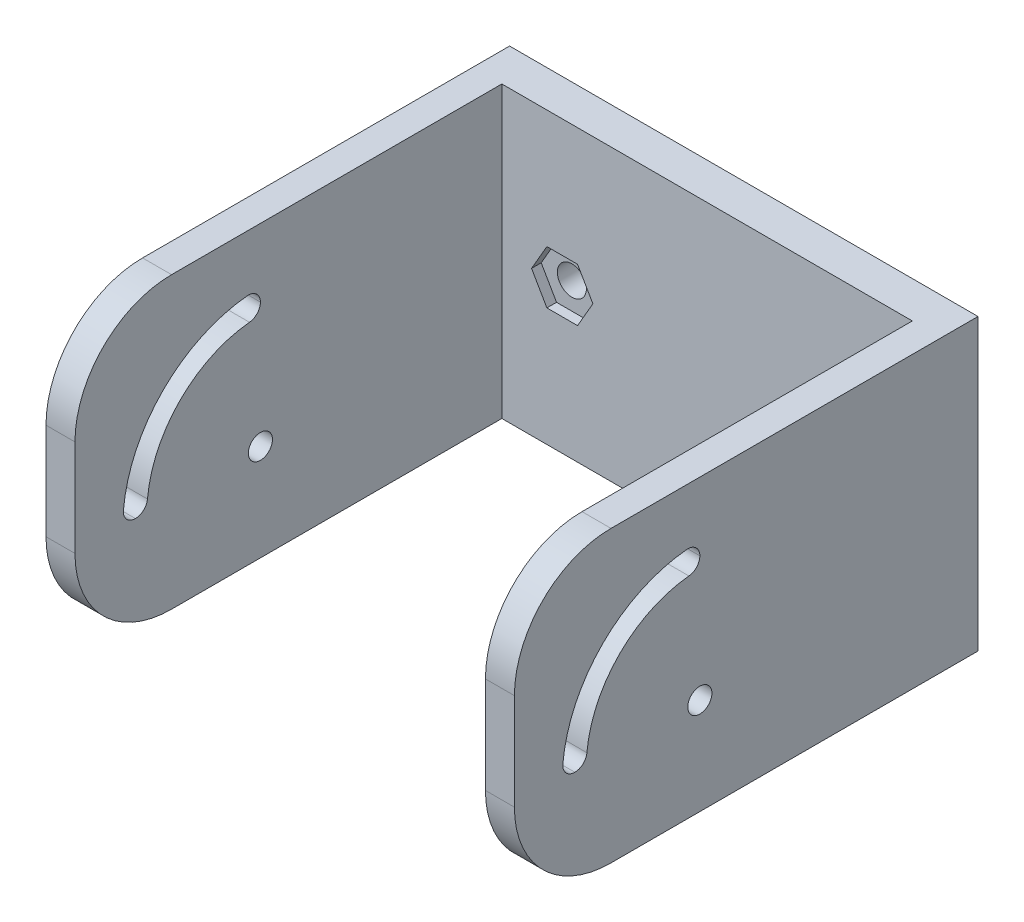
SolidWorks part; units mm, degrees
ref_plane "Front Plane" through (0, 0, 0) normal (0, 0, 1) x (1, 0, 0)
ref_plane "Top Plane" through (0, 0, 0) normal (0, 1, 0) x (1, 0, 0)
ref_plane "Right Plane" through (0, 0, 0) normal (1, 0, 0) x (0, 0, -1)
sketch "Sketch2" plane through (0, 0, 0) normal (0, 1, 0) x (1, 0, 0)
  line L0 (26.1154, 19.3846) -> (-22.3846, 19.3846)
  line L1 (-22.3846, 19.3846) -> (-22.3846, -28.6154)
  line L2 (-22.3846, -28.6154) -> (-19.3846, -28.6154)
  line L3 (-19.3846, -28.6154) -> (-19.3846, 15.5846)
  line L4 (-19.3846, 15.5846) -> (23.1154, 15.5846)
  line L5 (23.1154, 15.5846) -> (23.1154, -28.6154)
  line L6 (23.1154, -28.6154) -> (26.1154, -28.6154)
  line L7 (26.1154, -28.6154) -> (26.1154, 19.3846)
  dimension "D1" = 3
  dimension "D2" = 3
  dimension "D3" = 3.8
  dimension "D4" = 42.5
  dimension "D5" = 48
extrude "Boss-Extrude1" add sketch "Sketch2" along normal blind 30
sketch "Sketch3" plane through (-19.3846, 0, 0) normal (1, 0, 0) x (0, 0, -1)
  line L1 (15.5846, 30) -> (15.5846, 0) construction
  line L2 (-9.4154, 10) -> (-9.4154, 11.25)
  line L3 (-9.4154, 10) -> (-10.6654, 10)
  line L4 (-9.4154, 21.75) -> (-9.4154, 29.1907)
  line L5 (-21.1654, 10) -> (-23.6654, 10)
  line L6 (-28.6154, 0) -> (15.5846, 0) construction
  circle A0 centre (-9.4154, 10) radius 1.25
  arc A1 (-9.4154, 24.25) -> (-23.6654, 10) centre (-9.4154, 10) ccw
  arc A2 (-9.4154, 21.75) -> (-21.1654, 10) centre (-9.4154, 10) ccw
  point P11 (0, 0)
  dimension "D1" = 2.5
  dimension "D2" = 2.5
  dimension "D4" = 10.5
  dimension "D3" = 25
  dimension "D5" = 90
  dimension "D6" = 10
extrude "Cut-Extrude1" cut sketch "Sketch3" against normal blind 10 and the other way through all contours A2 L4 A1 L5 | L3 A0 L2 | L2 A0 L3 region at (-19.3846, 10.5305, 9.9459) region at (-19.3846, 9.8232, 9.2385) region at (-19.3846, 18.451, 17.8664)
sketch "Sketch4" plane through (0, 0, -19.3846) normal (0, 0, -1) x (-1, 0, 0)
  line L0 (-26.1154, 15) -> (22.3846, 15) construction
  line L1 (22.3846, 30) -> (22.3846, 0) construction
  line L2 (-1.8654, 30) -> (-1.8654, 0) construction
  line L3 (-26.1154, 30) -> (22.3846, 30) construction
  line L4 (-26.1154, 0) -> (22.3846, 0) construction
  line L5 (-26.1154, 30) -> (-26.1154, 0) construction
  circle A0 centre (-16.8654, 15) radius 1.5
  circle A1 centre (13.1346, 15) radius 1.5
  point P11 (-1.8654, 15)
  point P16 (0, 0)
  point P17 (-26.1154, 15)
  point P18 (0, 0)
  point P19 (0, 0)
  dimension "D1" = 3
  dimension "D2" = 15
  dimension "D3" = 15
extrude "Cut-Extrude2" cut sketch "Sketch4" against normal through all
fillet "Fillet1" radius 1.25 8 edges at (-20.8846, 24.25, 9.4154) (-20.8846, 21.75, 9.4154) (-20.8846, 10, 21.1654) (-20.8846, 10, 23.6654) (24.6154, 10, 23.6654) (24.6154, 10, 21.1654) (24.6154, 21.75, 9.4154) (24.6154, 24.25, 9.4154)
fillet "Fillet2" radius 10 4 edges at (24.6154, 0, 28.6154) (-20.8846, 0, 28.6154) (-20.8846, 30, 28.6154) (24.6154, 30, 28.6154)
sketch "Sketch5" plane through (0, 0, -15.5846) normal (0, 0, 1) x (1, 0, 0)
  line L1 (-14.7223, 12.25) -> (-11.5469, 12.25)
  line L2 (-11.5469, 12.25) -> (-9.9592, 15)
  line L3 (-9.9592, 15) -> (-11.5469, 17.75)
  line L4 (-11.5469, 17.75) -> (-14.7223, 17.75)
  line L5 (-14.7223, 17.75) -> (-16.31, 15)
  line L6 (-16.31, 15) -> (-14.7223, 12.25)
  line L7 (15.2777, 12.25) -> (18.4531, 12.25)
  line L8 (18.4531, 12.25) -> (20.0408, 15)
  line L9 (20.0408, 15) -> (18.4531, 17.75)
  line L10 (18.4531, 17.75) -> (15.2777, 17.75)
  line L11 (15.2777, 17.75) -> (13.69, 15)
  line L12 (13.69, 15) -> (15.2777, 12.25)
  circle A0 centre (-13.1346, 15) radius 2.75 construction
  circle A1 centre (16.8654, 15) radius 2.75 construction
  point P0 (-13.1346, 15)
  point P1 (16.8654, 15)
  dimension "D1" = 5.5
  dimension "D2" = 5.5
extrude "Cut-Extrude3" cut sketch "Sketch5" against normal blind 1
